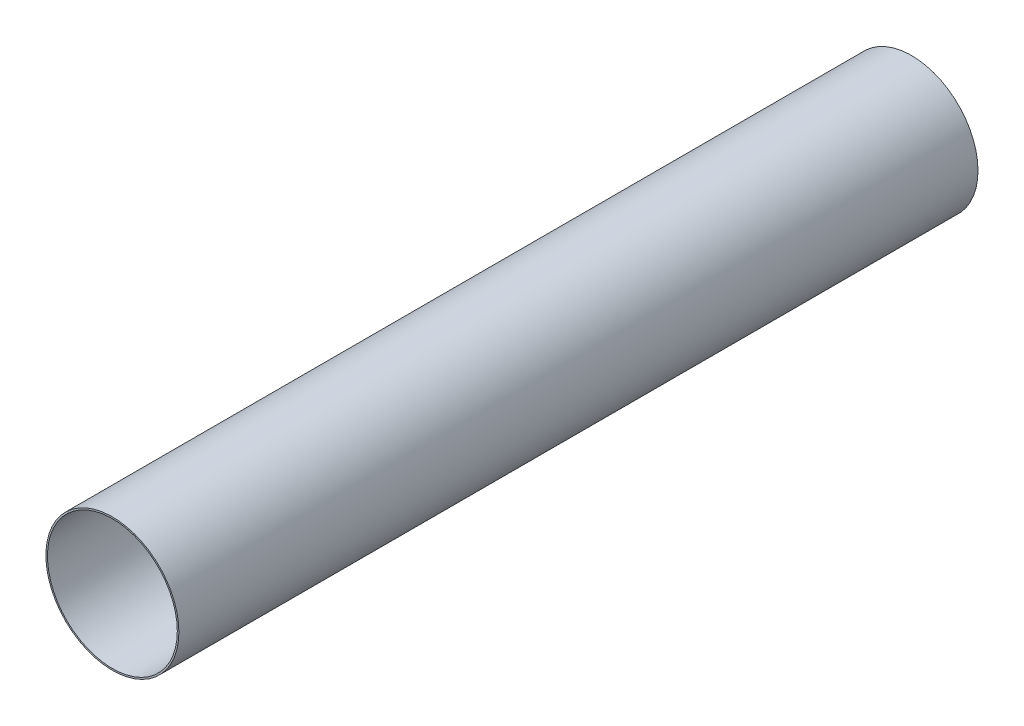
SolidWorks part; units mm, degrees
material "Thornel Mat VMA"
ref_plane "Front Plane" through (0, 0, 0) normal (0, 0, 1) x (1, 0, 0)
ref_plane "Top Plane" through (0, 0, 0) normal (0, 1, 0) x (1, 0, 0)
ref_plane "Right Plane" through (0, 0, 0) normal (1, 0, 0) x (0, 0, -1)
sketch "Sketch1" plane through (0, 0, 0) normal (0, 0, 1) x (1, 0, 0)
  circle A0 centre (0, 0) radius 84.55
  circle A1 centre (0, 0) radius 82.55
  dimension "D1" = 165.1
  dimension "D2" = 169.1
extrude "Boss-Extrude1" add sketch "Sketch1" along normal mid plane 1016
equation "\"TubeDiameter\" = 6.500in"
equation "\"D1@Sketch1\"=\"TubeDiameter\""
equation "\"D2@Sketch1\"=\"TubeDiameter\"+4mm"
